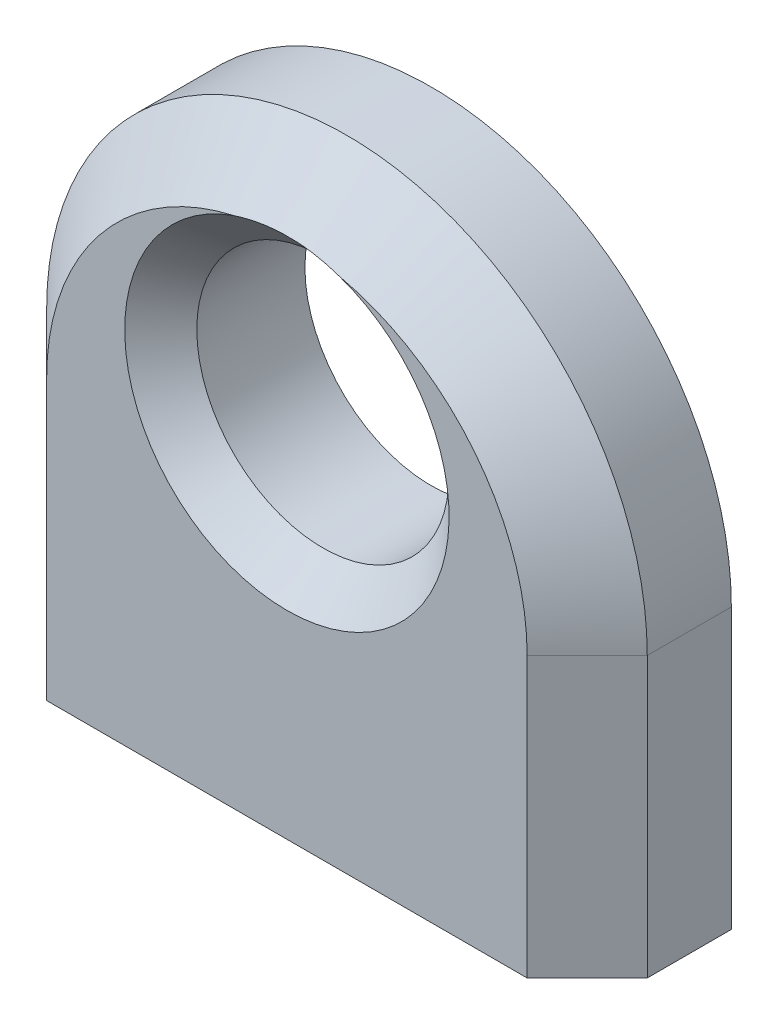
SolidWorks part; units mm, degrees
ref_plane "Front Plane" through (0, 0, 0) normal (0, 0, 1) x (1, 0, 0)
ref_plane "Top Plane" through (0, 0, 0) normal (0, 1, 0) x (1, 0, 0)
ref_plane "Right Plane" through (0, 0, 0) normal (1, 0, 0) x (0, 0, -1)
sketch "Sketch1" plane through (0, 0, 0) normal (0, 0, 1) x (1, 0, 0)
  line L0 (5, 0) -> (5, 4.9) construction
  line L5 (0, 0) -> (10, 0)
  line L6 (0, 0) -> (0, 4.6507)
  line L8 (10, 0) -> (10, 4.6507)
  arc A1 (0, 4.6507) -> (10, 4.6507) centre (5, 4.6507) cw
  point P0 (0, 0)
  dimension "D1" = 10
  dimension "D2" = 4.9
extrude "Boss-Extrude1" add sketch "Sketch1" along normal blind 2.4
ref_plane "Plane1" through (0, 0, 2.4) normal (0, 0, 1) x (1, 0, 0)
sketch "Sketch2" plane through (0, 0, 2.4) normal (0, 0, 1) x (1, 0, 0)
  line L0 (5, 0) -> (5, 6) construction
  line L1 (0, 0) -> (10, 0) construction
  circle A0 centre (5, 6) radius 2.1
  dimension "D1" = 6
  dimension "D2" = 4.2
extrude "Cut-Extrude1" cut sketch "Sketch2" against normal blind 3
chamfer "Chamfer1" distance 1 angle 45 3 edges at (10, 2.3254, 2.4) (5, 9.6507, 2.4) (0, 2.3254, 2.4)
chamfer "Chamfer2" distance 0.6 angle 45 1 edges at (7.1, 6, 2.4)
sketch "Sketch3" plane through (0, 0, 0) normal (0, 0, -1) x (-1, 0, 0)
  line L0 (-9.8189, 0.1902) -> (-0.2719, 0.1902) construction
  text T0 "out"
extrude "Cut-Extrude2" cut sketch "Sketch3" against normal blind 0.4
